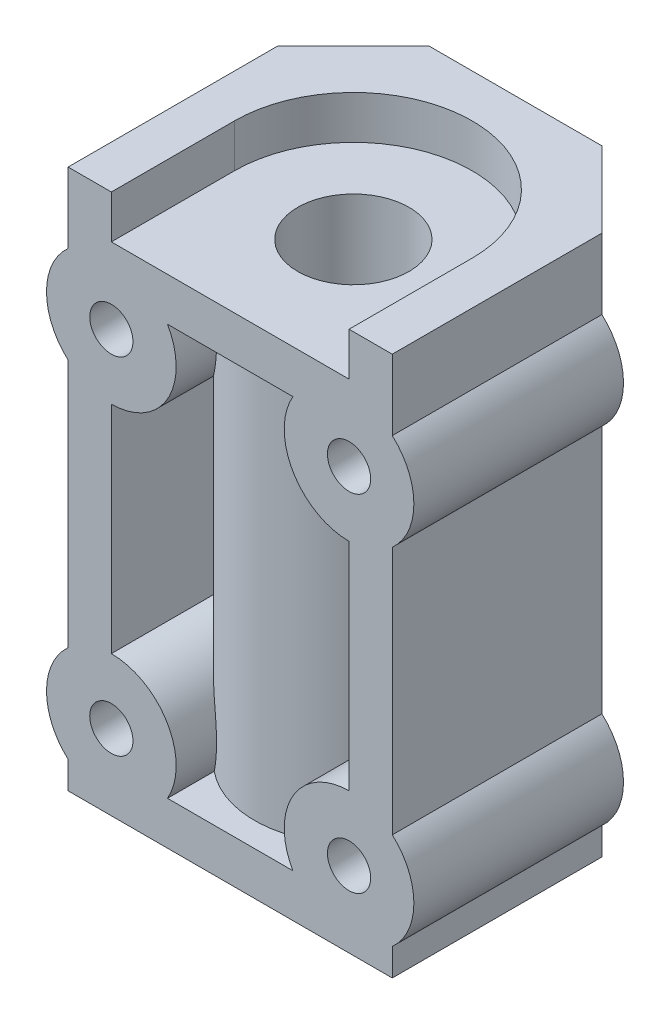
SolidWorks part; units mm, degrees
ref_plane "Front Plane" through (0, 0, 0) normal (0, 0, 1) x (1, 0, 0)
ref_plane "Top Plane" through (0, 0, 0) normal (0, 1, 0) x (1, 0, 0)
ref_plane "Right Plane" through (0, 0, 0) normal (1, 0, 0) x (0, 0, -1)
sketch "Sketch1" plane through (0, 0, 0) normal (0, 1, 0) x (1, 0, 0)
  line L0 (-15, -11.4) -> (15, -11.4)
  line L1 (0, 15) -> (0, -11.4) construction
  line L2 (-15, -11.4) -> (-15, 8)
  line L3 (-15, 8) -> (-8, 15)
  line L4 (-8, 15) -> (8, 15)
  line L5 (15, -11.4) -> (15, 8)
  line L6 (15, 8) -> (8, 15)
  circle A1 centre (0, 0) radius 5.15
  dimension "D2" = 10.3
  dimension "D3" = 11.4
  dimension "D4" = 30
  dimension "D5" = 45
  dimension "D6" = 15
  dimension "D7" = 7
extrude "Boss-Extrude1" add sketch "Sketch1" along normal blind 50
sketch "Sketch2" plane through (0, 50, 0) normal (0, 1, 0) x (1, 0, 0)
  line L0 (-11, 0) -> (-11, -11.4)
  line L1 (-15, -11.4) -> (15, -11.4) construction
  line L2 (-11, -11.4) -> (11, -11.4)
  line L3 (11, -11.4) -> (11, 0)
  circle A0 centre (0, 0) radius 11
  line M2 (-15, -11.4) -> (15, -11.4)
  circle M7 centre (0, 0) radius 5.15
  dimension "D1" = 22
extrude "Cut-Extrude1" cut sketch "Sketch2" against normal blind 4 contours A0 M7 | A0 L0 L3 M2 region at (0, 50, 11.2478) region at (0, 50, -10.6889)
sketch "Sketch3" plane through (0, 0, -15) normal (0, 0, -1) x (-1, 0, 0)
  line L0 (0, 50) -> (0, 0) construction
  line L1 (-8, 50) -> (8, 50) construction
  line L2 (-8, 23) -> (8, 23) construction
  line L3 (-8, 50) -> (-8, 0) construction
  line L4 (8, 50) -> (8, 0) construction
  line L5 (-8, 0) -> (8, 0) construction
  circle A0 centre (-11, 7) radius 2
  circle A1 centre (11, 7) radius 2
  circle A2 centre (-11, 39) radius 2
  circle A3 centre (11, 39) radius 2
  dimension "D1" = 4
  dimension "D2" = 22
  dimension "D3" = 32
  dimension "D4" = 7
extrude "Cut-Extrude2" cut sketch "Sketch3" against normal through all
shell "Shell1" thickness 4 removed face at (-9, 7, 11.4)
sketch "Sketch4" plane through (0, 0, 11.4) normal (0, 0, 1) x (1, 0, 0)
  line L0 (-15, 50) -> (-15, 0) construction
  line L1 (-15, 43.4721) -> (-15, 34.5279)
  line L2 (0, 50) -> (0, 23) construction
  line L3 (11, 50) -> (-11, 50) construction
  line L4 (0, 23) -> (-11, 23) construction
  line L5 (-11, 33) -> (-11, 13) construction
  line L6 (15, 43.4721) -> (15, 34.5279)
  line L7 (15, 2.5279) -> (15, 11.4721)
  line L8 (-15, 2.5279) -> (-15, 11.4721)
  arc A0 (-15, 43.4721) -> (-15, 34.5279) centre (-11, 39) ccw
  arc A2 (15, 43.4721) -> (15, 34.5279) centre (11, 39) cw
  arc A3 (15, 2.5279) -> (15, 11.4721) centre (11, 7) ccw
  arc A4 (-15, 2.5279) -> (-15, 11.4721) centre (-11, 7) cw
  dimension "D1" = 6
extrude "Boss-Extrude2" add sketch "Sketch4" against normal up to vertex (19.4 mm away) up to point (-15, 50, -8)
sketch "Sketch5" plane through (0, 0, -15) normal (0, 0, -1) x (-1, 0, 0)
  line L0 (0, 50) -> (0, 23) construction
  line L1 (-8, 50) -> (8, 50) construction
  line L2 (0, 23) -> (-14.2581, 23) construction
  line L3 (-15, 34.5279) -> (-15, 11.4721) construction
  circle A0 centre (-11, 39) radius 3.45
  circle A1 centre (11, 39) radius 3.45
  circle A2 centre (-11, 7) radius 3.45
  circle A3 centre (11, 7) radius 3.45
  point P11 (-15, 23)
  dimension "D1" = 6.9
extrude "Cut-Extrude3" cut sketch "Sketch5" against normal up to surface (7 mm away) up to face at (16, 39, -8)
